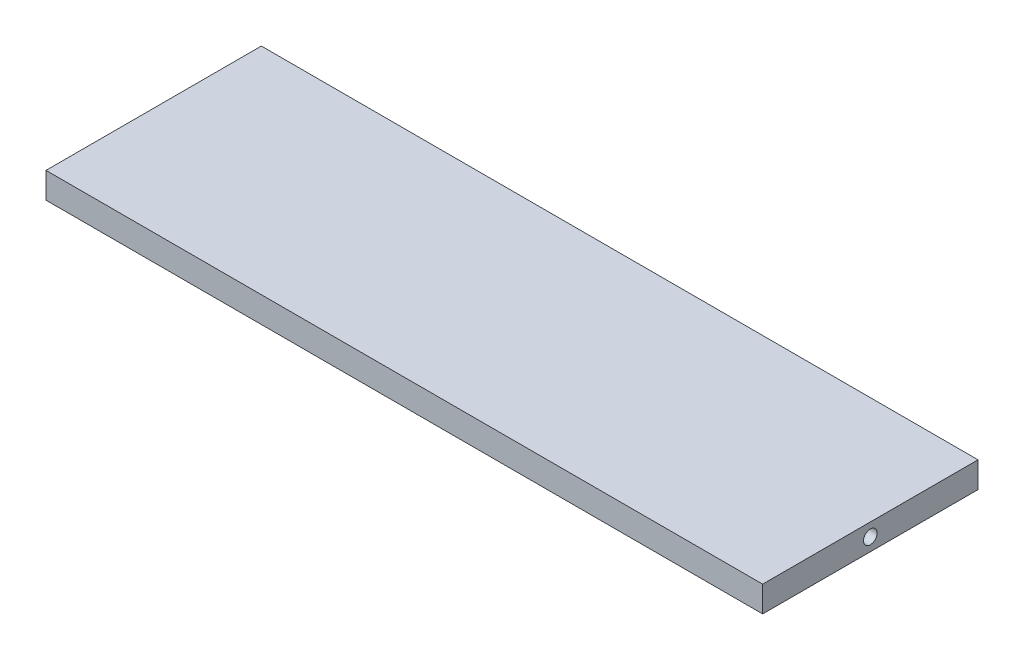
SolidWorks part; units mm, degrees
material "PLA"
ref_plane "Front" through (0, 0, 0) normal (0, 0, 1) x (1, 0, 0)
ref_plane "Top" through (0, 0, 0) normal (0, 1, 0) x (1, 0, 0)
ref_plane "Right" through (0, 0, 0) normal (1, 0, 0) x (0, 0, -1)
sketch "Sketch1" plane through (0, 0, 0) normal (0, 1, 0) x (1, 0, 0)
  line L1 (52.832, -15.875) -> (-52.832, -15.875)
  line L2 (52.832, -15.875) -> (52.832, 15.875)
  line L3 (52.832, 15.875) -> (-52.832, 15.875)
  line L4 (-52.832, -15.875) -> (-52.832, 15.875)
  line L5 (52.832, -15.875) -> (-52.832, 15.875) construction
  line L6 (52.832, 15.875) -> (-52.832, -15.875) construction
  point P0 (0, 0)
  dimension "D1" = 31.75
  dimension "D2" = 105.664
extrude "Boss-Extrude1" add sketch "Sketch1" along normal blind 3.81
sketch "Sketch2" plane through (0, 3.81, 0) normal (0, 1, 0) x (1, 0, 0)
  line L0 (-46.482, 3.175) -> (-46.482, 13.335)
  line L1 (-46.482, 13.335) -> (-10.946, 13.335)
  line L2 (-10.946, 13.335) -> (-46.482, 3.175)
  line L3 (52.832, 15.875) -> (-52.832, 15.875) construction
  line L4 (-52.832, 15.875) -> (-52.832, -15.875) construction
  line L5 (-46.482, -3.175) -> (-46.482, -13.335)
  line L6 (-46.482, -13.335) -> (-10.946, -13.335)
  line L7 (-10.946, -13.335) -> (-46.482, -3.175)
  line L8 (-52.832, -15.875) -> (52.832, -15.875) construction
  line L9 (10.922, 13.335) -> (46.482, 13.335)
  line L10 (46.482, 13.335) -> (46.482, 3.175)
  line L11 (46.482, 3.175) -> (10.922, 13.335)
  line L12 (52.832, -15.875) -> (52.832, 15.875) construction
  line L13 (46.482, -3.175) -> (46.482, -13.335)
  line L14 (46.482, -13.335) -> (10.922, -13.335)
  line L15 (10.922, -13.335) -> (46.482, -3.175)
  dimension "D1" = 10.16
  dimension "D2" = 2.54
  dimension "D3" = 6.35
  dimension "D4" = 35.536
  dimension "D5" = 35.536
  dimension "D6" = 2.54
  dimension "D7" = 10.16
  dimension "D8" = 35.56
  dimension "D9" = 6.35
  dimension "D10" = 10.16
  dimension "D11" = 35.56
  dimension "D12" = 10.16
sketch "Sketch4" plane through (52.832, 0, 0) normal (1, 0, 0) x (0, 0, -1)
  line L0 (0, 55) -> (0, -55) construction
  line L1 (55, 0) -> (-55, 0) construction
  circle A0 centre (0, 1.905) radius 1.0033
  dimension "D1" = 2.0066
  dimension "D2" = 1.905
extrude "Cut-Extrude3" cut sketch "Sketch4" against normal blind 7.62
sketch "Sketch5" plane through (-52.832, 0, 0) normal (-1, 0, 0) x (0, 0, 1)
  line L0 (0, -55) -> (0, 55) construction
  line L1 (55, 0) -> (-55, 0) construction
  circle A0 centre (0, 1.905) radius 1.0033
  dimension "D1" = 2.0066
  dimension "D2" = 1.905
extrude "Cut-Extrude4" cut sketch "Sketch5" against normal blind 7.62
